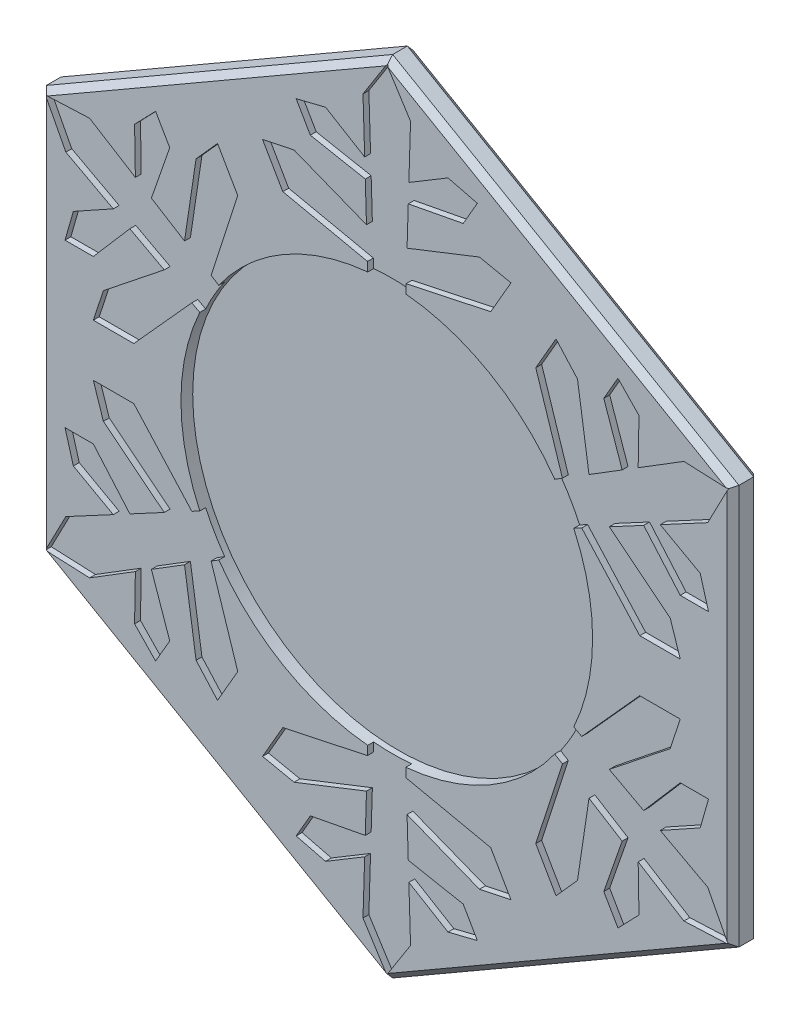
SolidWorks part; units mm, degrees
ref_plane "정면" through (0, 0, 0) normal (0, 0, 1) x (1, 0, 0)
ref_plane "윗면" through (0, 0, 0) normal (0, 1, 0) x (1, 0, 0)
ref_plane "우측면" through (0, 0, 0) normal (1, 0, 0) x (0, 0, -1)
sketch "스케치1" plane through (0, 0, 0) normal (0, 0, 1) x (1, 0, 0)
  line L0 (0, 0) -> (-56.2917, 32.5)
  line L1 (58.8897, -34) -> (58.8897, 34)
  line L2 (58.8897, 34) -> (0, 68)
  line L3 (0, 68) -> (-58.8897, 34)
  line L4 (-58.8897, 34) -> (-58.8897, -34)
  line L5 (-58.8897, -34) -> (0, -68)
  line L6 (0, -68) -> (58.8897, -34)
  line L7 (56.2917, 32.5) -> (0, 0)
  line L8 (0, -65) -> (0, 0)
  line L9 (-56.2917, 32.5) -> (-56.2917, -32.5)
  line L10 (-56.2917, -32.5) -> (0, -65)
  line L11 (0, -65) -> (56.2917, -32.5)
  line L12 (56.2917, -32.5) -> (56.2917, 32.5)
  line L13 (56.2917, 32.5) -> (0, 65)
  line L14 (0, 65) -> (-56.2917, 32.5)
  circle A1 centre (0, 0) radius 58.8897 construction
  point P1 (-58, 34.641)
  point P11 (0, -5)
  point P15 (0, -10)
  point P17 (-59, 32.909)
  point P20 (0, -15)
  point P21 (0, -20)
  point P22 (0, -25)
  point P23 (0, -30)
  point P24 (0, -35)
  point P25 (0, -40)
  point P26 (0, -45)
  point P27 (0, -50)
  point P28 (0, -55)
  point P29 (0, -60)
  point P32 (-4.3301, 2.3594)
  point P33 (-8.6603, 4.8594)
  point P34 (-12.9904, 7.3594)
  point P35 (-17.3205, 9.8594)
  point P36 (-21.6506, 12.3594)
  point P37 (-25.9808, 14.8594)
  point P38 (-30.3109, 17.3594)
  point P39 (-34.641, 19.8594)
  point P40 (-38.9711, 22.3594)
  point P41 (-43.3013, 24.8594)
  point P42 (-47.6314, 27.3594)
  point P43 (-51.9615, 29.8594)
  point P44 (4.2083, 2.4297)
  point P45 (8.5385, 4.9297)
  point P46 (12.8686, 7.4297)
  point P47 (17.1987, 9.9297)
  point P48 (21.5289, 12.4297)
  point P49 (25.859, 14.9297)
  point P50 (30.1891, 17.4297)
  point P51 (34.5192, 19.9297)
  point P52 (38.8494, 22.4297)
  point P53 (43.1795, 24.9297)
  point P54 (47.5096, 27.4297)
  point P55 (51.8397, 29.9297)
  point P56 (-0.0406, -0.0703)
  dimension "D1" = 65
  dimension "D2" = 5
  dimension "D3" = 12
  dimension "D4" = 3
  dimension "D5" = 65
  dimension "D6" = 65
  dimension "D7" = 65
  dimension "D8" = 68
extrude "보스-돌출1" add sketch "스케치1" along normal blind 5.5 contours L4 L5 L6 L1 L2 L3
sketch "스케치6" plane through (0, 0, 5.5) normal (0, 0, 1) x (1, 0, 0)
  line L1 (-58.8897, 34) -> (-58.0516, 33.5161)
  line L2 (-58.8897, 34) -> (-58.8897, -34)
  line L3 (0, 0) -> (-58.8897, 0) construction
  line L4 (-58.8897, -34) -> (0, -68)
  line L5 (0, -68) -> (0, 0)
  line L6 (0, 0) -> (-29.4449, -51) construction
  line L7 (-33.1527, -15.3513) -> (-27.313, -12.2197)
  line L8 (-54.5739, -26.8389) -> (-46.5066, -22.5127)
  line L9 (-46.5066, -22.5127) -> (-53.2967, -18.748)
  line L10 (-53.2967, -18.748) -> (-54.7146, -13.8014)
  line L11 (-54.7146, -13.8014) -> (-49.9016, -13.8014)
  line L12 (-49.9016, -13.8014) -> (-43.6834, -20.9987)
  line L13 (-37.8382, -17.864) -> (-48.1939, -9.622)
  line L14 (-48.1939, -9.622) -> (-49.9016, -4.4211)
  line L15 (-49.9016, -4.4211) -> (-43.0161, -4.4211)
  line L16 (-43.0161, -4.4211) -> (-33.1527, -15.3513)
  line L17 (-27.313, -12.2197) -> (-30.9566, -8.576)
  line L18 (-30.9566, -8.576) -> (-32.1611, -3.8066)
  line L19 (-32.1611, -3.8066) -> (-26.7746, -3.8066)
  line L20 (-26.7746, -3.8066) -> (-23.3909, -10.1164)
  line L21 (-18.0861, -7.2716) -> (-19.9799, -3.7402)
  line L22 (-24.196, 4.1218) -> (-21.0805, 5.7925)
  line L23 (-21.0805, 5.7925) -> (-19.9799, 3.7402)
  line L24 (-11.6248, -3.8066) -> (-14.9706, 0)
  line L25 (8.9871, -15.5661) -> (12.3358, -10.1645)
  line L26 (-12.1952, 0) -> (-9.7385, -2.795)
  line L27 (-50.5302, -33.8429) -> (-42.7498, -29.0196)
  line L28 (-6.0976, -10.5614) -> (-7.2898, -7.0363)
  line L29 (-43.6834, 20.9987) -> (-37.8382, 17.864)
  line L30 (-9.109, -8.1641) -> (-7.4853, -12.9649)
  line L31 (-5.5238, -21.1525) -> (-6.7509, -19.1732)
  line L32 (-8.5285, -23.0152) -> (-5.5238, -21.1525)
  line L33 (-15.3404, -12.0272) -> (-13.229, -15.433)
  line L34 (-16.6839, -21.2842) -> (-20.4564, -15.1989)
  line L35 (-19.3771, -25.9491) -> (-16.6839, -21.2842)
  line L36 (-22.9054, -22.5212) -> (-19.3771, -25.9491)
  line L37 (-24.239, -17.5439) -> (-22.9054, -22.5212)
  line L38 (-25.3368, -35.0424) -> (-29.871, -21.0354)
  line L39 (-28.7796, -41.0055) -> (-25.3368, -35.0424)
  line L40 (-32.4298, -36.9262) -> (-28.7796, -41.0055)
  line L41 (-34.3898, -23.8368) -> (-32.4298, -36.9262)
  line L42 (-36.9032, -36.3154) -> (-40.0271, -27.3316)
  line L43 (-39.3097, -40.4835) -> (-36.9032, -36.3154)
  line L44 (-42.8846, -36.7823) -> (-39.3097, -40.4835)
  line L45 (-42.7498, -29.0196) -> (-42.8846, -36.7823)
  line L48 (-50.5302, 33.8429) -> (-42.7498, 29.0196)
  line L49 (-42.7498, 29.0196) -> (-42.8846, 36.7823)
  line L50 (-42.8846, 36.7823) -> (-39.3097, 40.4835)
  line L51 (-39.3097, 40.4835) -> (-36.9032, 36.3154)
  line L52 (-36.9032, 36.3154) -> (-40.0271, 27.3316)
  line L53 (-34.3898, 23.8368) -> (-32.4298, 36.9262)
  line L54 (-32.4298, 36.9262) -> (-28.7796, 41.0055)
  line L55 (-28.7796, 41.0055) -> (-25.3368, 35.0424)
  line L56 (-25.3368, 35.0424) -> (-29.871, 21.0354)
  line L57 (-24.239, 17.5439) -> (-22.9054, 22.5212)
  line L58 (-22.9054, 22.5212) -> (-19.3771, 25.9491)
  line L59 (-19.3771, 25.9491) -> (-16.6839, 21.2842)
  line L60 (-16.6839, 21.2842) -> (-20.4564, 15.1989)
  line L61 (-15.3404, 12.0272) -> (-13.229, 15.433)
  line L62 (-9.109, 8.1641) -> (-7.4853, 12.9649)
  line L63 (-40.0271, 27.3316) -> (-34.3898, 23.8368)
  line L64 (-6.0976, 10.5614) -> (-7.2898, 7.0363)
  line L65 (-54.5739, 26.8389) -> (-46.5066, 22.5127)
  line L66 (-12.1952, 0) -> (-9.7385, 2.795)
  line L67 (-14.9706, 0) -> (-12.1952, 0)
  line L68 (-11.6248, 3.8066) -> (-14.9706, 0)
  line L69 (-21.0805, -5.7925) -> (-19.9799, -3.7402)
  line L70 (-24.196, -4.1218) -> (-21.0805, -5.7925)
  line L71 (-18.0861, 7.2716) -> (-19.9799, 3.7402)
  line L72 (-26.7746, 3.8066) -> (-23.3909, 10.1164)
  line L73 (-32.1611, 3.8066) -> (-26.7746, 3.8066)
  line L74 (-30.9566, 8.576) -> (-32.1611, 3.8066)
  line L75 (-27.313, 12.2197) -> (-30.9566, 8.576)
  line L76 (-43.0161, 4.4211) -> (-33.1527, 15.3513)
  line L77 (-49.9016, 4.4211) -> (-43.0161, 4.4211)
  line L78 (-48.1939, 9.622) -> (-49.9016, 4.4211)
  line L79 (-37.8382, 17.864) -> (-48.1939, 9.622)
  line L80 (-49.9016, 13.8014) -> (-43.6834, 20.9987)
  line L81 (-54.7146, 13.8014) -> (-49.9016, 13.8014)
  line L82 (-53.2967, 18.748) -> (-54.7146, 13.8014)
  line L83 (-46.5066, 22.5127) -> (-53.2967, 18.748)
  line L85 (-5.5238, 21.1525) -> (-6.7509, 19.1732)
  line L86 (-8.5285, 23.0152) -> (-5.5238, 21.1525)
  line L88 (4.0438, 60.6819) -> (3.7568, 51.5322)
  line L89 (3.7568, 51.5322) -> (10.4121, 55.5303)
  line L90 (10.4121, 55.5303) -> (15.4049, 54.285)
  line L91 (15.4049, 54.285) -> (12.9984, 50.1168)
  line L92 (12.9984, 50.1168) -> (3.6563, 48.3303)
  line L93 (3.4484, 41.7008) -> (15.7641, 46.5482)
  line L94 (15.7641, 46.5482) -> (21.122, 45.4266)
  line L95 (21.122, 45.4266) -> (17.6792, 39.4635)
  line L96 (17.6792, 39.4635) -> (3.2817, 36.3867)
  line L97 (3.0739, 29.7636) -> (8.0512, 31.0972)
  line L98 (8.0512, 31.0972) -> (12.784, 29.7556)
  line L99 (12.784, 29.7556) -> (10.0907, 25.0908)
  line L100 (10.0907, 25.0908) -> (2.9344, 25.3153)
  line L101 (2.7457, 19.2988) -> (6.7509, 19.1732)
  line L102 (2.5158, 11.9706) -> (7.4853, 12.9649)
  line L103 (-29.871, 21.0354) -> (-24.239, 17.5439)
  line L104 (6.0976, 10.5614) -> (2.4487, 9.8313)
  line L105 (-4.0438, 60.6819) -> (-3.7568, 51.5322)
  line L106 (-6.0976, 10.5614) -> (-2.4487, 9.8313)
  line L107 (-33.1527, 15.3513) -> (-27.313, 12.2197)
  line L108 (-2.5158, 11.9706) -> (-7.4853, 12.9649)
  line L109 (-15.5567, 15.36) -> (-13.229, 15.433)
  line L110 (-15.6676, 18.8935) -> (-15.5567, 15.36)
  line L111 (-2.7457, 19.2988) -> (-6.7509, 19.1732)
  line L112 (-10.0907, 25.0908) -> (-2.9344, 25.3153)
  line L113 (-12.784, 29.7556) -> (-10.0907, 25.0908)
  line L114 (-8.0512, 31.0972) -> (-12.784, 29.7556)
  line L115 (-3.0739, 29.7636) -> (-8.0512, 31.0972)
  line L116 (-17.6792, 39.4635) -> (-3.2817, 36.3867)
  line L117 (-21.122, 45.4266) -> (-17.6792, 39.4635)
  line L118 (-15.7641, 46.5482) -> (-21.122, 45.4266)
  line L119 (-3.4484, 41.7008) -> (-15.7641, 46.5482)
  line L120 (-12.9984, 50.1168) -> (-3.6563, 48.3303)
  line L121 (-15.4049, 54.285) -> (-12.9984, 50.1168)
  line L122 (-10.4121, 55.5303) -> (-15.4049, 54.285)
  line L123 (-3.7568, 51.5322) -> (-10.4121, 55.5303)
  line L125 (15.5567, 15.36) -> (13.229, 15.433)
  line L126 (15.6676, 18.8935) -> (15.5567, 15.36)
  line L128 (54.5739, 26.8389) -> (46.5066, 22.5127)
  line L129 (46.5066, 22.5127) -> (53.2967, 18.748)
  line L130 (53.2967, 18.748) -> (54.7146, 13.8014)
  line L131 (54.7146, 13.8014) -> (49.9016, 13.8014)
  line L132 (49.9016, 13.8014) -> (43.6834, 20.9987)
  line L133 (37.8382, 17.864) -> (48.1939, 9.622)
  line L134 (48.1939, 9.622) -> (49.9016, 4.4211)
  line L135 (49.9016, 4.4211) -> (43.0161, 4.4211)
  line L136 (43.0161, 4.4211) -> (33.1527, 15.3513)
  line L137 (27.313, 12.2197) -> (30.9566, 8.576)
  line L138 (30.9566, 8.576) -> (32.1611, 3.8066)
  line L139 (32.1611, 3.8066) -> (26.7746, 3.8066)
  line L140 (26.7746, 3.8066) -> (23.3909, 10.1164)
  line L141 (18.0861, 7.2716) -> (19.9799, 3.7402)
  line L142 (11.6248, 3.8066) -> (14.9706, 0)
  line L143 (-20.4564, 15.1989) -> (-15.3404, 12.0272)
  line L144 (12.1952, 0) -> (9.7385, 2.795)
  line L145 (50.5302, 33.8429) -> (42.7498, 29.0196)
  line L146 (6.0976, 10.5614) -> (7.2898, 7.0363)
  line L147 (7.2898, 7.0363) -> (3.6372, 4.7719)
  line L148 (9.109, 8.1641) -> (7.4853, 12.9649)
  line L149 (5.5238, 21.1525) -> (6.7509, 19.1732)
  line L150 (8.5285, 23.0152) -> (5.5238, 21.1525)
  line L151 (15.3404, 12.0272) -> (13.229, 15.433)
  line L152 (16.6839, 21.2842) -> (20.4564, 15.1989)
  line L153 (19.3771, 25.9491) -> (16.6839, 21.2842)
  line L154 (22.9054, 22.5212) -> (19.3771, 25.9491)
  line L155 (24.239, 17.5439) -> (22.9054, 22.5212)
  line L156 (25.3368, 35.0424) -> (29.871, 21.0354)
  line L157 (28.7796, 41.0055) -> (25.3368, 35.0424)
  line L158 (32.4298, 36.9262) -> (28.7796, 41.0055)
  line L159 (34.3898, 23.8368) -> (32.4298, 36.9262)
  line L160 (36.9032, 36.3154) -> (40.0271, 27.3316)
  line L161 (39.3097, 40.4835) -> (36.9032, 36.3154)
  line L162 (42.8846, 36.7823) -> (39.3097, 40.4835)
  line L163 (42.7498, 29.0196) -> (42.8846, 36.7823)
  line L165 (21.0805, -5.7925) -> (19.9799, -3.7402)
  line L166 (24.196, -4.1218) -> (21.0805, -5.7925)
  line L168 (50.5302, -33.8429) -> (42.7498, -29.0196)
  line L169 (42.7498, -29.0196) -> (42.8846, -36.7823)
  line L170 (42.8846, -36.7823) -> (39.3097, -40.4835)
  line L171 (39.3097, -40.4835) -> (36.9032, -36.3154)
  line L172 (36.9032, -36.3154) -> (40.0271, -27.3316)
  line L173 (34.3898, -23.8368) -> (32.4298, -36.9262)
  line L174 (32.4298, -36.9262) -> (28.7796, -41.0055)
  line L175 (28.7796, -41.0055) -> (25.3368, -35.0424)
  line L176 (25.3368, -35.0424) -> (29.871, -21.0354)
  line L177 (24.239, -17.5439) -> (22.9054, -22.5212)
  line L178 (22.9054, -22.5212) -> (19.3771, -25.9491)
  line L179 (19.3771, -25.9491) -> (16.6839, -21.2842)
  line L180 (16.6839, -21.2842) -> (20.4564, -15.1989)
  line L181 (15.3404, -12.0272) -> (13.229, -15.433)
  line L182 (9.109, -8.1641) -> (7.4853, -12.9649)
  line L183 (-23.3909, 10.1164) -> (-18.0861, 7.2716)
  line L184 (6.0976, -10.5614) -> (7.2898, -7.0363)
  line L185 (54.5739, -26.8389) -> (46.5066, -22.5127)
  line L186 (12.1952, 0) -> (9.7385, -2.795)
  line L187 (-3.6563, 48.3303) -> (-3.4484, 41.7008)
  line L188 (11.6248, -3.8066) -> (14.9706, 0)
  line L189 (21.0805, 5.7925) -> (19.9799, 3.7402)
  line L190 (24.196, 4.1218) -> (21.0805, 5.7925)
  line L191 (18.0861, -7.2716) -> (19.9799, -3.7402)
  line L192 (26.7746, -3.8066) -> (23.3909, -10.1164)
  line L193 (32.1611, -3.8066) -> (26.7746, -3.8066)
  line L194 (30.9566, -8.576) -> (32.1611, -3.8066)
  line L195 (27.313, -12.2197) -> (30.9566, -8.576)
  line L196 (43.0161, -4.4211) -> (33.1527, -15.3513)
  line L197 (49.9016, -4.4211) -> (43.0161, -4.4211)
  line L198 (48.1939, -9.622) -> (49.9016, -4.4211)
  line L199 (37.8382, -17.864) -> (48.1939, -9.622)
  line L200 (49.9016, -13.8014) -> (43.6834, -20.9987)
  line L201 (54.7146, -13.8014) -> (49.9016, -13.8014)
  line L202 (53.2967, -18.748) -> (54.7146, -13.8014)
  line L203 (46.5066, -22.5127) -> (53.2967, -18.748)
  line L205 (5.5238, -21.1525) -> (6.7509, -19.1732)
  line L206 (8.5285, -23.0152) -> (5.5238, -21.1525)
  line L208 (-4.0438, -60.6819) -> (-3.7568, -51.5322)
  line L209 (-3.7568, -51.5322) -> (-10.4121, -55.5303)
  line L210 (-10.4121, -55.5303) -> (-15.4049, -54.285)
  line L211 (-15.4049, -54.285) -> (-12.9984, -50.1168)
  line L212 (-12.9984, -50.1168) -> (-3.6563, -48.3303)
  line L213 (-3.4484, -41.7008) -> (-15.7641, -46.5482)
  line L214 (-15.7641, -46.5482) -> (-21.122, -45.4266)
  line L215 (-21.122, -45.4266) -> (-17.6792, -39.4635)
  line L216 (-17.6792, -39.4635) -> (-3.2817, -36.3867)
  line L217 (-3.0739, -29.7636) -> (-8.0512, -31.0972)
  line L218 (-8.0512, -31.0972) -> (-12.784, -29.7556)
  line L219 (-12.784, -29.7556) -> (-10.0907, -25.0908)
  line L220 (-10.0907, -25.0908) -> (-2.9344, -25.3153)
  line L221 (-2.7457, -19.2988) -> (-6.7509, -19.1732)
  line L222 (-2.5158, -11.9706) -> (-7.4853, -12.9649)
  line L223 (-7.4853, -12.9649) -> (-6.0976, -10.5614)
  line L224 (-6.0976, -10.5614) -> (-2.4487, -9.8313)
  line L225 (4.0438, -60.6819) -> (3.7568, -51.5322)
  line L226 (6.0976, -10.5614) -> (2.4487, -9.8313)
  line L227 (3.6563, 48.3303) -> (3.4484, 41.7008)
  line L228 (2.5158, -11.9706) -> (7.4853, -12.9649)
  line L229 (15.5567, -15.36) -> (13.229, -15.433)
  line L230 (15.6676, -18.8935) -> (15.5567, -15.36)
  line L231 (2.7457, -19.2988) -> (6.7509, -19.1732)
  line L232 (10.0907, -25.0908) -> (2.9344, -25.3153)
  line L233 (12.784, -29.7556) -> (10.0907, -25.0908)
  line L234 (8.0512, -31.0972) -> (12.784, -29.7556)
  line L235 (3.0739, -29.7636) -> (8.0512, -31.0972)
  line L236 (17.6792, -39.4635) -> (3.2817, -36.3867)
  line L237 (21.122, -45.4266) -> (17.6792, -39.4635)
  line L238 (15.7641, -46.5482) -> (21.122, -45.4266)
  line L239 (3.4484, -41.7008) -> (15.7641, -46.5482)
  line L240 (12.9984, -50.1168) -> (3.6563, -48.3303)
  line L241 (15.4049, -54.285) -> (12.9984, -50.1168)
  line L242 (10.4121, -55.5303) -> (15.4049, -54.285)
  line L243 (3.7568, -51.5322) -> (10.4121, -55.5303)
  line L245 (-15.5567, -15.36) -> (-13.229, -15.433)
  line L246 (-15.6676, -18.8935) -> (-15.5567, -15.36)
  line L247 (-10.9928, 19.0401) -> (-15.6676, 18.8935)
  line L248 (-10.9928, 19.0401) -> (-8.5285, 23.0152)
  line L249 (-8.9871, 15.5661) -> (-12.3358, 10.1645)
  line L250 (-8.9871, 15.5661) -> (-2.6348, 15.7653)
  line L251 (10.9928, 19.0401) -> (15.6676, 18.8935)
  line L252 (8.9871, 15.5661) -> (12.3358, 10.1645)
  line L253 (10.9928, 19.0401) -> (8.5285, 23.0152)
  line L254 (8.9871, 15.5661) -> (2.6348, 15.7653)
  line L255 (17.9742, 0) -> (14.9706, -5.6008)
  line L256 (21.9856, 0) -> (24.196, -4.1218)
  line L257 (17.9742, 0) -> (14.9706, 5.6008)
  line L258 (21.9856, 0) -> (24.196, 4.1218)
  line L259 (8.9871, -15.5661) -> (2.6348, -15.7653)
  line L260 (10.9928, -19.0401) -> (15.6676, -18.8935)
  line L261 (10.9928, -19.0401) -> (8.5285, -23.0152)
  line L262 (-10.9928, -19.0401) -> (-8.5285, -23.0152)
  line L263 (-8.9871, -15.5661) -> (-2.6348, -15.7653)
  line L264 (-8.9871, -15.5661) -> (-12.3358, -10.1645)
  line L265 (-10.9928, -19.0401) -> (-15.6676, -18.8935)
  line L266 (-21.9856, 0) -> (-24.196, 4.1218)
  line L267 (-21.9856, 0) -> (-24.196, -4.1218)
  line L268 (-17.9742, 0) -> (-14.9706, -5.6008)
  line L269 (-17.9742, 0) -> (-14.9706, 5.6008)
  line L270 (-50.5302, 33.8429) -> (-58.0516, 33.5161)
  line L271 (-58.0516, 33.5161) -> (-54.5739, 26.8389)
  line L272 (4.0438, 60.6819) -> (0, 67.0322)
  line L273 (0, 67.0322) -> (-4.0438, 60.6819)
  line L274 (-3.2817, 36.3867) -> (-3.0739, 29.7636)
  line L275 (3.2817, 36.3867) -> (3.0739, 29.7636)
  line L276 (-2.9344, 25.3153) -> (-2.7457, 19.2988)
  line L277 (2.9344, 25.3153) -> (2.7457, 19.2988)
  line L278 (-2.6348, 15.7653) -> (-2.5158, 11.9706)
  line L279 (2.6348, 15.7653) -> (2.5158, 11.9706)
  line L280 (-2.4487, 9.8313) -> (-2.314, 5.5358)
  line L281 (2.4487, 9.8313) -> (2.314, 5.5358)
  line L282 (9.7385, 2.795) -> (5.9512, 0.764)
  line L283 (9.7385, -2.795) -> (5.9512, -0.764)
  line L284 (7.2898, -7.0363) -> (3.6372, -4.7719)
  line L285 (-2.4487, -9.8313) -> (-2.314, -5.5358)
  line L286 (2.4487, -9.8313) -> (2.314, -5.5358)
  line L287 (-7.2898, -7.0363) -> (-3.6372, -4.7719)
  line L288 (-9.7385, -2.795) -> (-5.9512, -0.764)
  line L289 (-9.7385, 2.795) -> (-5.9512, 0.764)
  line L290 (-7.2898, 7.0363) -> (-3.6372, 4.7719)
  line L291 (12.3358, -10.1645) -> (9.109, -8.1641)
  line L292 (14.9706, -5.6008) -> (11.6248, -3.8066)
  line L293 (2.6348, -15.7653) -> (2.5158, -11.9706)
  line L294 (-2.6348, -15.7653) -> (-2.5158, -11.9706)
  line L295 (-12.3358, -10.1645) -> (-9.109, -8.1641)
  line L296 (-14.9706, -5.6008) -> (-11.6248, -3.8066)
  line L297 (-14.9706, 5.6008) -> (-11.6248, 3.8066)
  line L298 (-12.3358, 10.1645) -> (-9.109, 8.1641)
  line L299 (20.4564, -15.1989) -> (15.3404, -12.0272)
  line L300 (23.3909, -10.1164) -> (18.0861, -7.2716)
  line L301 (33.1527, -15.3513) -> (27.313, -12.2197)
  line L302 (29.871, -21.0354) -> (24.239, -17.5439)
  line L303 (40.0271, -27.3316) -> (34.3898, -23.8368)
  line L304 (43.6834, -20.9987) -> (37.8382, -17.864)
  line L305 (3.2817, -36.3867) -> (2.7457, -19.2988)
  line L306 (-3.2817, -36.3867) -> (-2.7457, -19.2988)
  line L307 (-3.6563, -48.3303) -> (-3.4484, -41.7008)
  line L308 (3.6563, -48.3303) -> (3.4484, -41.7008)
  line L309 (-29.871, -21.0354) -> (-24.239, -17.5439)
  line L310 (-40.0271, -27.3316) -> (-34.3898, -23.8368)
  line L311 (-43.6834, -20.9987) -> (-37.8382, -17.864)
  line L312 (-23.3909, -10.1164) -> (-18.0861, -7.2716)
  line L313 (-20.4564, -15.1989) -> (-15.3404, -12.0272)
  line L314 (14.9706, 5.6008) -> (11.6248, 3.8066)
  line L315 (12.3358, 10.1645) -> (9.109, 8.1641)
  line L316 (20.4564, 15.1989) -> (15.3404, 12.0272)
  line L317 (23.3909, 10.1164) -> (18.0861, 7.2716)
  line L318 (33.1527, 15.3513) -> (27.313, 12.2197)
  line L319 (29.871, 21.0354) -> (24.239, 17.5439)
  line L320 (40.0271, 27.3316) -> (34.3898, 23.8368)
  line L321 (43.6834, 20.9987) -> (37.8382, 17.864)
  line L322 (54.5739, 26.8389) -> (58.0516, 33.5161)
  line L323 (58.0516, 33.5161) -> (50.5302, 33.8429)
  line L324 (50.5302, -33.8429) -> (58.0516, -33.5161)
  line L325 (58.0516, -33.5161) -> (54.5739, -26.8389)
  line L326 (-4.0438, -60.6819) -> (0, -67.0322)
  line L327 (0, -67.0322) -> (4.0438, -60.6819)
  line L328 (-54.5739, -26.8389) -> (-58.0516, -33.5161)
  line L329 (-58.0516, -33.5161) -> (-50.5302, -33.8429)
  arc A0 (2.314, -5.5358) -> (3.6372, -4.7719) centre (0, 0) ccw
  arc A1 (-3.6372, -4.7719) -> (-2.314, -5.5358) centre (0, 0) ccw
  arc A2 (-5.9512, 0.764) -> (-5.9512, -0.764) centre (0, 0) ccw
  arc A3 (-2.314, 5.5358) -> (-3.6372, 4.7719) centre (0, 0) ccw
  arc A4 (3.6372, 4.7719) -> (2.314, 5.5358) centre (0, 0) ccw
  arc A5 (5.9512, -0.764) -> (5.9512, 0.764) centre (0, 0) ccw
  point P319 (0, 0)
  point P353 (0, 0)
  dimension "D1" = 12
extrude "컷-돌출8" cut sketch "스케치6" against normal blind 1
sketch "스케치7" plane through (0, 0, 0) normal (0, 0, -1) x (-1, 0, 0)
  circle A0 centre (0, 0) radius 37.5
extrude "컷-돌출9" cut sketch "스케치7" against normal blind 1
sketch "스케치8" plane through (0, 0, 0) normal (0, 0, -1) x (-1, 0, 0)
  circle A0 centre (0, 0) radius 35
  dimension "D1" = 70
extrude "컷-돌출10" cut sketch "스케치8" against normal blind 2
chamfer "모따기1" distance 1 angle 45 12 edges at (29.4449, -51, 5.5) (-29.4449, -51, 5.5) (-58.8897, 0, 5.5) (-29.4449, 51, 5.5) (29.4449, 51, 5.5) (58.8897, 0, 5.5) (29.4449, -51, 1) (-29.4449, -51, 1) (-58.8897, 0, 1) (-29.4449, 51, 1) (58.8897, 0, 1) (29.4449, 51, 1)
sketch "스케치10" plane through (0, 0, 5.5) normal (0, 0, 1) x (1, 0, 0)
  circle A0 centre (0, 0) radius 35
  dimension "D1" = 70
extrude "컷-돌출11" cut sketch "스케치10" against normal blind 2
sketch "스케치11" plane through (0, 0, 1) normal (0, 0, -1) x (-1, 0, 0)
  line L0 (0, 0) -> (-58.8897, -34) construction
  line L1 (-51.9102, -24.1671) -> (-54.4363, -22.923)
  line L2 (-54.4363, -22.923) -> (-54.4363, -17.3983)
  line L3 (-54.4363, -17.3983) -> (-46.9469, -21.0869)
  line L4 (-46.9469, -21.0869) -> (-42.2855, -18.0642)
  line L5 (-42.2855, -18.0642) -> (-53.7394, -12.423)
  line L6 (-53.7394, -12.423) -> (-53.7394, -7.7486)
  line L7 (-53.7394, -7.7486) -> (-37.4503, -16.1948)
  line L8 (-37.4503, -16.1948) -> (-34.4196, -14.8842)
  line L9 (-51.9102, -24.1671) -> (-51.9102, -26.3884)
  line L10 (-51.9102, -26.3884) -> (-55.5489, -28.9572)
  line L11 (-55.5489, -28.9572) -> (-55.5489, -32.0712)
  line L12 (-43.7782, -27.4918) -> (-31.7573, -19.9429)
  line L13 (-44.7436, -29.164) -> (-43.7782, -27.4918)
  line L14 (-47.6286, -27.4984) -> (-44.7436, -29.164)
  line L15 (-33.4464, -23.0903) -> (-30.8602, -21.3049)
  line L16 (-52.3921, -31.8043) -> (-53.7394, -31.0265)
  line L17 (-48.9211, -29.7372) -> (-52.3921, -31.8043)
  line L18 (-34.7292, -39.8898) -> (-33.4464, -23.0903)
  line L19 (-36.2892, -38.9891) -> (-34.7292, -39.8898)
  line L20 (-35.1293, -23.7992) -> (-36.2892, -38.9891)
  line L21 (-43.0619, -28.9291) -> (-35.1293, -23.7992)
  line L22 (-43.5894, -36.1109) -> (-43.0619, -28.9291)
  line L23 (-50.2137, -22.923) -> (-50.2137, -27.4984)
  line L24 (-50.2137, -22.923) -> (-53.0677, -21.5434)
  line L25 (-53.0677, -21.5434) -> (-53.0677, -19.6941)
  line L26 (-53.0677, -19.6941) -> (-46.5843, -22.8282)
  line L27 (-46.5843, -22.8282) -> (-38.1753, -18.5233)
  line L28 (-38.1753, -18.5233) -> (-51.9102, -11.9328)
  line L29 (-51.9102, -11.9328) -> (-51.9102, -10.1315)
  line L30 (-51.9102, -10.1315) -> (-36.72, -17.4203)
  line L31 (-50.2137, -27.4984) -> (-53.7394, -29.4707)
  line L32 (-53.7394, -29.4707) -> (-53.7394, -31.0265)
  line L33 (-36.72, -17.4203) -> (-33.8807, -16.0733)
  line L34 (-47.6286, -27.4984) -> (-47.6286, -24.1671)
  line L35 (-47.6286, -24.1671) -> (-45.6977, -24.1671)
  line L36 (-45.6977, -24.1671) -> (-33.1498, -17.5312)
  line L37 (-45.191, -35.1862) -> (-43.5894, -36.1109)
  line L38 (-44.9588, -32.0249) -> (-45.191, -35.1862)
  line L39 (-44.9588, -32.0249) -> (-48.9211, -29.7372)
  line L40 (-52.8521, -33.6282) -> (-55.5489, -32.0712)
  line L41 (-48.8081, -31.7613) -> (-52.8521, -33.6282)
  line L42 (-46.8844, -32.8719) -> (-48.8081, -31.7613)
  line L43 (-32.7502, -24.3355) -> (-30.0999, -22.3661)
  line L44 (-33.5802, -42.6654) -> (-32.7502, -24.3355)
  line L45 (-37.6284, -40.3282) -> (-33.5802, -42.6654)
  line L46 (-36.7868, -27.5883) -> (-37.6284, -40.3282)
  line L47 (-41.7353, -30.1137) -> (-36.7868, -27.5883)
  line L48 (-42.2855, -38.444) -> (-41.7353, -30.1137)
  line L49 (-47.07, -35.6817) -> (-42.2855, -38.444)
  line L50 (-46.8844, -32.8719) -> (-47.07, -35.6817)
  line L306 (0, 0) -> (-58.8897, 0) construction
  line L307 (-58.8897, -34) -> (-58.8897, 34) construction
  line L308 (-37.0673, 5.6805) -> (-40.6278, 7.7486)
  line L309 (-40.6278, 7.7486) -> (-50.2137, 0)
  line L310 (-46.5843, 0) -> (-40.6278, 4.7875)
  line L311 (-40.6278, 4.7875) -> (-37.3709, 3.1096)
  line L312 (-42.878, 0) -> (-40.4123, 2.1946)
  line L313 (-40.4123, 2.1946) -> (-37.4789, 1.2565)
  line L314 (-37.0673, -5.6805) -> (-40.6278, -7.7486)
  line L315 (-40.6278, -4.7875) -> (-37.3709, -3.1096)
  line L316 (-40.4123, -2.1946) -> (-37.4789, -1.2565)
  line L317 (-42.878, 0) -> (-40.4123, -2.1946)
  line L318 (-46.5843, 0) -> (-40.6278, -4.7875)
  line L319 (-40.6278, -7.7486) -> (-50.2137, 0)
  circle A1 centre (0, 0) radius 37.5 construction
  circle A2 centre (0, 0) radius 37.5 construction
  circle A3 centre (0, 0) radius 37.5
  point P338 (0, 0)
  point P431 (0, 0)
  point P442 (0, 0)
  circle M322 centre (0, 0) radius 37.5
extrude "보스-돌출2" add sketch "스케치11" along normal blind 1 contours L319 L314 L315 L318 L310 L311 L308 L309 M322 | L312 L317 L316 L313 M322 | L42 L50 L49 L48 L47 L46 L45 L44 L43 L15 L18 L19 L20 L21 L22 L37 L38 L39 L17 L16 L32 L31 L23 L24 L25 L26 L27 L28 L29 L30 L33 L8 L7 L6 L5 L4 L3 L2 L1 L9 L10 L11 L40 L41 M322 | L36 L35 L34 L14 L13 L12 M322
pattern_circular "원형 패턴1" count 6 over 360 about axis through (0, 0, 0) along (0, 0, 1) of "보스-돌출2"
